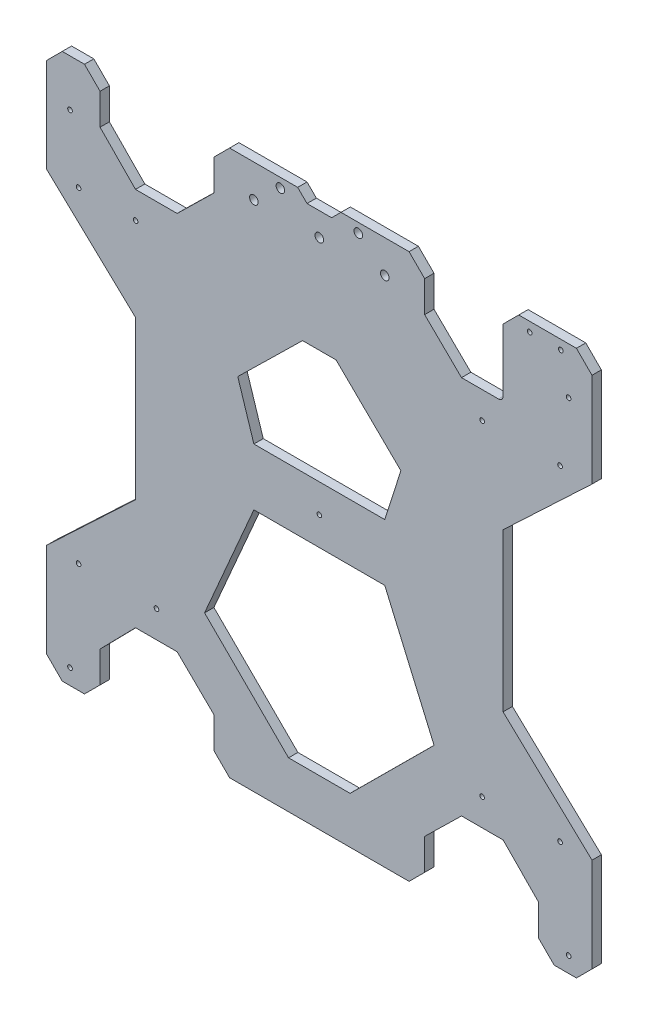
SolidWorks part; units mm, degrees
material "6063-T5"
ref_plane "Piano frontale" through (0, 0, 0) normal (0, 0, 1) x (1, 0, 0)
ref_plane "Piano superiore" through (0, 0, 0) normal (0, 1, 0) x (1, 0, 0)
ref_plane "Piano destro" through (0, 0, 0) normal (1, 0, 0) x (0, 0, -1)
sketch "Schizzo13" plane through (0, 0, 0) normal (0, 0, 1) x (1, 0, 0)
  line L0 (175, 350) -> (175, 0) construction
  line L1 (10, 0) -> (24.282, 0)
  line L2 (0, 279.5) -> (57.0808, 225.6111)
  line L3 (217, 193.2869) -> (227.343, 225.6111)
  line L4 (133, 193.2869) -> (217, 193.2869)
  line L5 (350, 175) -> (0, 175) construction
  line L6 (-60.1887, 10) -> (461.2643, 10) construction
  line L7 (279.5, 279.5) -> (279.5, 175) construction
  line L8 (-12.961, 344) -> (386.8832, 344) construction
  line L9 (-12.961, 329) -> (386.8832, 329) construction
  line L10 (161.1089, 350) -> (167.1089, 344)
  line L11 (279.5, 70.5) -> (175, 70.5) construction
  line L12 (70.5, 70.5) -> (175, 70.5) construction
  line L13 (167.1089, 344) -> (182.8911, 344)
  line L14 (57.0808, 279.5) -> (57.0808, 175) construction
  line L15 (57.0808, 279.5) -> (175, 279.5) construction
  line L16 (175, 279.5) -> (329.5, 279.5) construction
  line L17 (329.5, 70.5) -> (329.5, 279.5) construction
  line L18 (20.5, 70.5) -> (329.5, 70.5) construction
  line L19 (20.5, 70.5) -> (20.5, 279.5) construction
  line L20 (175, 279.5) -> (20.5, 279.5) construction
  line L21 (15, -40.9714) -> (15, 408.5301) construction
  line L22 (335, -40.9714) -> (335, 408.5301) construction
  line L23 (-12.961, 320) -> (386.8832, 320) construction
  line L24 (10, 0) -> (0, 10)
  line L25 (340, 0) -> (350, 10)
  line L26 (107.4046, 340) -> (107.4046, 320)
  line L27 (107.4046, 320) -> (83.7454, 296.8073)
  line L28 (57.0808, 279.5) -> (20.5, 279.5) construction
  line L29 (57.0174, 296.8073) -> (34.282, 320)
  line L30 (83.7454, 296.8073) -> (57.0174, 296.8073)
  line L31 (34.282, 320) -> (34.282, 340)
  line L32 (24.282, 350) -> (10, 350)
  line L33 (133, 193.2869) -> (122.657, 225.6111)
  line L34 (57.0808, 279.5) -> (57.0808, 350) construction
  line L35 (164.2491, 266.3832) -> (185.7509, 266.3832)
  line L36 (122.657, 225.6111) -> (164.2491, 266.3832)
  line L37 (57.0808, 225.6111) -> (57.0808, 175)
  line L38 (227.343, 225.6111) -> (185.7509, 266.3832)
  line L39 (292.9192, 225.6111) -> (292.9192, 124.3889)
  line L40 (350, 279.5) -> (292.9192, 225.6111)
  line L41 (188.8911, 350) -> (182.8911, 344)
  line L42 (117.4046, 350) -> (161.1089, 350)
  line L44 (292.9826, 299.8073) -> (292.9826, 340)
  line L46 (117.4046, 0) -> (232.5954, 0)
  line L47 (266.2546, 296.8073) -> (289.9826, 296.8073)
  line L48 (242.5954, 320) -> (266.2546, 296.8073)
  line L49 (242.5954, 340) -> (242.5954, 320)
  line L50 (350, 70.5) -> (292.9192, 124.3889)
  line L53 (350, 10) -> (350, 70.5)
  line L55 (315.718, 30) -> (315.718, 10)
  line L56 (292.9826, 53.1927) -> (315.718, 30)
  line L57 (266.2546, 53.1927) -> (292.9826, 53.1927)
  line L58 (242.5954, 30) -> (266.2546, 53.1927)
  line L59 (242.5954, 10) -> (242.5954, 30)
  line L60 (107.4046, 10) -> (107.4046, 30)
  line L61 (107.4046, 30) -> (83.7454, 53.1927)
  line L62 (83.7454, 53.1927) -> (57.0174, 53.1927)
  line L63 (57.0174, 53.1927) -> (34.282, 30)
  line L64 (34.282, 30) -> (34.282, 10)
  line L66 (0, 10) -> (0, 70.5)
  line L69 (0, 70.5) -> (57.0808, 124.3889)
  line L70 (57.0808, 124.3889) -> (57.0808, 175)
  line L71 (0, 279.5) -> (0, 340)
  line L72 (188.8911, 350) -> (232.5954, 350)
  line L73 (302.9826, 350) -> (340, 350)
  line L74 (350, 279.5) -> (350, 340)
  line L75 (325.718, 0) -> (340, 0)
  line L76 (24.282, 0) -> (34.282, 10)
  line L77 (117.4046, 0) -> (107.4046, 10)
  line L78 (232.5954, 0) -> (242.5954, 10)
  line L79 (315.718, 10) -> (325.718, 0)
  line L80 (10, 350) -> (0, 340)
  line L81 (24.282, 350) -> (34.282, 340)
  line L82 (107.4046, 340) -> (117.4046, 350)
  line L83 (232.5954, 350) -> (242.5954, 340)
  line L84 (292.9826, 340) -> (302.9826, 350)
  line L85 (340, 350) -> (350, 340)
  line L86 (133, 156.7131) -> (101.3482, 83.6168)
  line L87 (101.3482, 83.6168) -> (155.2542, 30)
  line L88 (155.2542, 30) -> (194.7458, 30)
  line L89 (133, 156.7131) -> (217, 156.7131)
  line L90 (248.6518, 83.6168) -> (194.7458, 30)
  line L91 (217, 156.7131) -> (248.6518, 83.6168)
  circle A0 centre (15, 320) radius 1.5
  circle A1 centre (20.5, 279.5) radius 1.5
  circle A2 centre (57.0808, 279.5) radius 1.5
  circle A3 centre (175, 175) radius 1.5
  arc A4 (289.9826, 296.8073) -> (292.9826, 299.8073) centre (289.9826, 299.8073) ccw
  circle A5 centre (20.5, 70.5) radius 1.5
  circle A6 centre (200, 344) radius 2.75
  circle A7 centre (150, 344) radius 2.75
  circle A8 centre (175, 329) radius 2.75
  circle A9 centre (217, 329) radius 2.75
  circle A10 centre (133, 329) radius 2.75
  circle A11 centre (70.5, 70.5) radius 1.5
  circle A12 centre (279.5, 70.5) radius 1.5
  circle A13 centre (329.5, 70.5) radius 1.5
  circle A14 centre (335, 10) radius 1.5
  circle A15 centre (15, 10) radius 1.5
  circle A16 centre (279.5, 279.5) radius 1.5
  circle A17 centre (329.5, 279.5) radius 1.5
  circle A18 centre (335, 320) radius 1.5
  circle A19 centre (310, 344) radius 1.5
  circle A20 centre (330, 344) radius 1.5
  point P7 (175, 175)
  point P25 (175, 344)
  point P30 (175, 329)
  point P41 (175, 175)
  point P43 (329.5, 175)
  point P46 (15, 320)
  point P54 (335, 320)
  point P55 (335, 10)
  point P56 (15, 10)
  point P57 (15, 320)
  point P58 (335, 320)
  point P59 (15, 10)
  point P60 (335, 10)
  point P93 (292.9826, 296.8073)
  point P108 (175, 344)
  point P155 (175, 156.7131)
  point P156 (175, 30)
  dimension "D5" = 42
  dimension "D6" = 5.5
  dimension "D7" = 25
  dimension "D8" = 15
  dimension "D10" = 154.5
  dimension "D3" = 104.5
  dimension "D17" = 20
  dimension "D2" = 3
  dimension "D4" = 104.5
  dimension "D11" = 104.5
  dimension "D15" = 310
  dimension "D16" = 320
extrude "Estrusione-Estrusione2" add sketch "Schizzo13" against normal blind 6
sketch "Schizzo14" plane through (0, 0, 0) normal (0, 0, 1) x (1, 0, 0)
  line L0 (350, 350.0234) -> (0, 350.0234)
  line L2 (0, 350.0234) -> (0, 0)
  line L3 (0, 0) -> (350, 0)
  line L4 (117.4046, 0) -> (232.5954, 0) construction
  line L5 (175, 344) -> (175, 0) construction
  line L6 (350, 350.0234) -> (350, 0)
  line L7 (182.8911, 344) -> (167.1089, 344) construction
  circle A0 centre (175, 223.4858) radius 4.4409
  circle A1 centre (175, 78.9698) radius 4.6362
sketch "Schizzo15" plane through (0, 0, 0) normal (0, 0, 1) x (1, 0, 0)
  text T0 "HackerBot" font "Lobster 1.4" height 14
